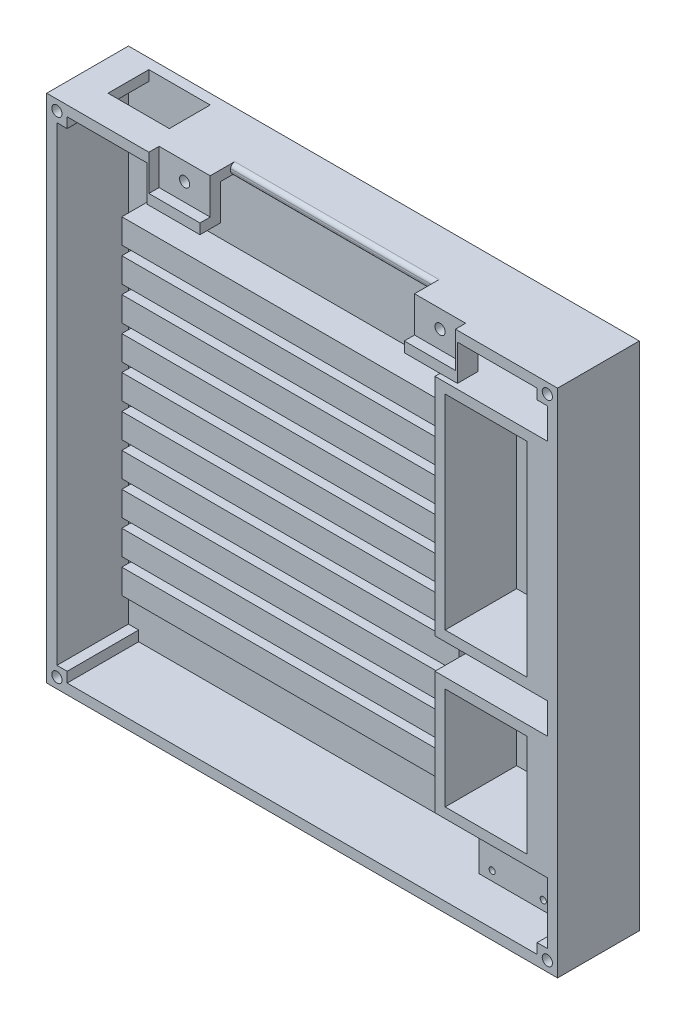
SolidWorks part; units mm, degrees
ref_plane "Ebene vorne" through (0, 0, 0) normal (0, 0, 1) x (1, 0, 0)
ref_plane "Ebene oben" through (0, 0, 0) normal (0, 1, 0) x (1, 0, 0)
ref_plane "Ebene rechts" through (0, 0, 0) normal (1, 0, 0) x (0, 0, -1)
sketch "Sketch1" plane through (0, 0, 0) normal (0, 0, 1) x (1, 0, 0)
  line L1 (0, 0) -> (-250, 0)
  line L2 (0, 0) -> (0, 250)
  line L3 (0, 250) -> (-250, 250)
  line L4 (-250, 0) -> (-250, 250)
  dimension "D1" = 250
  dimension "D2" = 250
extrude "Boss-Extrude1" add sketch "Sketch1" along normal blind 50
sketch "Sketch2" plane through (0, 0, 50) normal (0, 0, 1) x (1, 0, 0)
  line L0 (-125, 250) -> (-125, 0) construction
  line L1 (0, 250) -> (-250, 250) construction
  line L2 (-250, 0) -> (0, 0) construction
  line L5 (0, 0) -> (0, 250) construction
  line L7 (-55, 220) -> (-15, 220)
  line L8 (-55, 220) -> (-55, 120)
  line L9 (-55, 120) -> (-15, 120)
  line L10 (-15, 220) -> (-15, 120)
  line L14 (-55, 95) -> (-15, 95)
  line L15 (-55, 95) -> (-55, 45)
  line L16 (-55, 45) -> (-15, 45)
  line L17 (-15, 95) -> (-15, 45)
  dimension "D1" = 100
  dimension "D2" = 40
  dimension "D3" = 30
  dimension "D4" = 15
  dimension "D5" = 50
  dimension "D6" = 25
extrude "Cut-Extrude1" cut sketch "Sketch2" against normal blind 45
fillet "Fillet1" radius 5 4 edges at (-35, 120, 50) (-15, 170, 50) (-55, 170, 50) (-35, 220, 50)
fillet "Fillet2" radius 5 4 edges at (-35, 45, 50) (-15, 70, 50) (-35, 95, 50) (-55, 70, 50)
sketch "Sketch4" plane through (0, 0, 50) normal (0, 0, 1) x (1, 0, 0)
  line L0 (0, 250) -> (-250, 250) construction
  line L1 (-200, 250) -> (-175, 250)
  line L2 (-200, 250) -> (-200, 232.5)
  line L3 (-200, 232.5) -> (-175, 232.5)
  line L4 (-175, 250) -> (-175, 232.5)
  line L5 (-125, 250) -> (-125, 0) construction
  line L10 (-250, 0) -> (0, 0) construction
  line L11 (-50, 232.5) -> (-75, 232.5)
  line L12 (-75, 250) -> (-75, 232.5)
  line L13 (-50, 250) -> (-75, 250)
  line L14 (-50, 250) -> (-50, 232.5)
  dimension "D1" = 50
  dimension "D2" = 25
  dimension "D3" = 17.5
sketch "Sketch5" plane through (0, 0, 50) normal (0, 0, 1) x (1, 0, 0)
  line L0 (-233.25, 198.25) -> (-68.25, 198.25) construction
  line L2 (-68.25, 198.25) -> (-68.25, 33.25) construction
  line L3 (-68.25, 33.25) -> (-233.25, 33.25) construction
  line L4 (-233.25, 33.25) -> (-233.25, 198.25) construction
  line L5 (-250, 250) -> (-250, 0) construction
  line L9 (-233.25, 198.25) -> (-216.75, 198.25) construction
  line L10 (-233.25, 198.25) -> (-233.25, 181.75) construction
  line L11 (-233.25, 181.75) -> (-216.75, 181.75) construction
  line L12 (-216.75, 198.25) -> (-216.75, 181.75) construction
  line L13 (-233.25, 198.25) -> (-216.75, 181.75) construction
  line L14 (-233.25, 181.75) -> (-216.75, 198.25) construction
  line L16 (0, 250) -> (-250, 250) construction
  circle A0 centre (-225, 190) radius 6.25
  dimension "D5" = 12.5
  dimension "D1" = 165
  dimension "D2" = 51.75
  dimension "D3" = 16.75
  dimension "D4" = 165
  dimension "D6" = 16.5
  dimension "D7" = 16.5
extrude "Cut-Extrude2" cut sketch "Sketch5" against normal blind 22
fillet "Fillet5" radius 1.5 1 edges at (-218.75, 190, 50)
pattern_linear "LPattern4" count 10 spacing 16.5 along (1, 0, 0) count 10 spacing 16.5 along (0, -1, 0) of "Cut-Extrude2", "Fillet5"
sketch "Sketch7" plane through (0, 0, 0) normal (0, 0, -1) x (-1, 0, 0)
  line L0 (250, 250) -> (250, 0) construction
  line L1 (5, 245) -> (245, 245)
  line L2 (5, 245) -> (5, 225)
  line L3 (5, 5) -> (245, 5)
  line L4 (245, 245) -> (245, 5)
  line L5 (0, 250) -> (250, 250) construction
  line L6 (0, 0) -> (0, 250) construction
  line L7 (250, 0) -> (0, 0) construction
  line L8 (5, 115) -> (5, 100)
  line L9 (5, 225) -> (60, 225)
  line L11 (5, 115) -> (60, 115)
  line L12 (60, 225) -> (60, 115)
  line L13 (5, 40) -> (60, 40)
  line L15 (5, 100) -> (60, 100)
  line L16 (60, 40) -> (60, 100)
  line L17 (5, 40) -> (5, 5)
  line L18 (60, 225) -> (10, 225) construction
  dimension "D1" = 5
  dimension "D2" = 5
  dimension "D3" = 5
  dimension "D4" = 5
extrude "Cut-Extrude4" cut sketch "Sketch7" against normal blind 45
sketch "Sketch8" plane through (0, 0, 50) normal (0, 0, 1) x (1, 0, 0)
  line L0 (0, 250) -> (-250, 250) construction
  line L1 (-175, 250) -> (-75, 250)
  line L2 (-175, 250) -> (-175, 230)
  line L3 (-175, 230) -> (-75, 230)
  line L4 (-75, 250) -> (-75, 230)
  point P6 (-125, 250)
  point P7 (-125, 250)
  dimension "D1" = 100
  dimension "D2" = 20
extrude "Cut-Extrude5" cut sketch "Sketch8" against normal blind 20
fillet "Fillet6" radius 2.5 2 edges at (-125, 230, 45) (-125, 230, 50)
fillet "Fillet7" radius 2 2 edges at (-125, 250, 30) (-125, 245, 30)
sketch "Sketch10" plane through (0, 0, 50) normal (0, 0, 1) x (1, 0, 0)
  line L2 (-35, 40) -> (-35, 0) construction
  line L3 (-10, 40) -> (-60, 40) construction
  line L4 (-250, 0) -> (0, 0) construction
  circle A0 centre (-35, 20) radius 13.5
  dimension "D1" = 27
extrude "Cut-Extrude6" cut sketch "Sketch10" against normal through all
extrude "Cut-Extrude7" cut sketch "Sketch4" against normal blind 10
sketch "Sketch12" plane through (0, 0, 45) normal (0, 0, -1) x (-1, 0, 0)
  line L0 (17.3, 19.25) -> (51.5, 19.25) construction
  line L1 (17.3, 32.5) -> (51.5, 32.5) construction
  line L2 (17.3, 32.5) -> (17.3, 6) construction
  line L3 (17.3, 6) -> (51.5, 6) construction
  line L4 (51.5, 32.5) -> (51.5, 6) construction
  line L5 (35, 40) -> (35, 0) construction
  line L6 (17.3, 20) -> (51.5, 20) construction
  circle A0 centre (46.4, 29.3) radius 2.5
  circle A2 centre (20.1, 29.3) radius 2.5
  circle A3 centre (20.1, 29.3) radius 1.5
  circle A4 centre (46.4, 29.3) radius 1.5
  circle A5 centre (20.1, 9.2) radius 1.5
  circle A6 centre (20.1, 9.2) radius 2.5
  circle A7 centre (46.4, 9.2) radius 1.5
  circle A8 centre (46.4, 9.2) radius 2.5
  dimension "D3" = 5
  dimension "D4" = 2.8
  dimension "D5" = 3.2
  dimension "D6" = 5
  dimension "D7" = 5.1
  dimension "D9" = 3
  dimension "D10" = 3
  dimension "D1" = 34.2
  dimension "D2" = 26.5
  dimension "D8" = 3.2
  dimension "D11" = 16.5
  dimension "D12" = 13.25
  dimension "D13" = 14
fillet "Verrundung1" radius 2.5 2 edges at (-48.5, 20, 45) (-21.5, 20, 50)
sketch "Skizze2" plane through (0, 245, 0) normal (0, -1, 0) x (1, 0, 0)
  line L0 (-175, 28) -> (-175, 40) construction
  line L1 (-175, 40) -> (-200, 40)
  line L2 (-175, 40) -> (-175, 35)
  line L3 (-175, 35) -> (-200, 35)
  line L4 (-200, 40) -> (-200, 35)
  line L5 (-200, 40) -> (-175, 40) construction
  line L6 (-125, 50) -> (-125, 0) construction
  line L7 (-250, 50) -> (0, 50) construction
  line L8 (-250, 0) -> (0, 0) construction
  line L9 (-50, 40) -> (-50, 35)
  line L10 (-75, 35) -> (-50, 35)
  line L11 (-75, 40) -> (-75, 35)
  line L12 (-75, 40) -> (-50, 40)
  dimension "D1" = 25
  dimension "D2" = 5
extrude "Aufsatz-Linear austragen1" add sketch "Skizze2" along normal blind 12.5
sketch "Skizze4" plane through (0, 0, 45) normal (0, 0, -1) x (-1, 0, 0)
  line L0 (75, 232.5) -> (75, 227.5) construction
  line L1 (50, 232.5) -> (75, 232.5)
  line L3 (49, 227.5) -> (75, 227.5)
  line L4 (75, 232.5) -> (75, 227.5)
  line L5 (175, 227.5) -> (175, 232.5) construction
  line L6 (200, 232.5) -> (175, 232.5)
  line L8 (201, 227.5) -> (175, 227.5)
  line L9 (175, 232.5) -> (175, 227.5)
  line L10 (50, 245) -> (5, 245) construction
  line L12 (50, 232.5) -> (50, 245)
  line L13 (50, 245) -> (49, 245)
  line L14 (49, 227.5) -> (49, 245)
  line L15 (245, 245) -> (200, 245) construction
  line L17 (200, 232.5) -> (200, 245)
  line L18 (200, 245) -> (201, 245)
  line L19 (201, 227.5) -> (201, 245)
  dimension "D1" = 5
  dimension "D2" = 5
  dimension "D3" = 1
  dimension "D4" = 1
extrude "Aufsatz-Linear austragen2" add sketch "Skizze4" along normal blind 10
sketch "Skizze11" plane through (0, 0, 50) normal (0, 0, 1) x (1, 0, 0)
  line L1 (-232.75, 197.75) -> (-68.75, 197.75)
  line L2 (-232.75, 197.75) -> (-232.75, 33.75)
  line L3 (-232.75, 33.75) -> (-68.75, 33.75)
  line L4 (-68.75, 197.75) -> (-68.75, 33.75)
  circle A0 centre (-175.5, 190) radius 7.75 construction
  circle A1 centre (-225, 173.5) radius 7.75 construction
  circle A2 centre (-76.5, 157) radius 7.75 construction
  circle A3 centre (-159, 41.5) radius 7.75 construction
extrude "Schnitt-Linear austragen6" cut sketch "Skizze11" against normal blind 10
sketch "Skizze12" plane through (0, 0, 50) normal (0, 0, 1) x (1, 0, 0)
  line L18 (-237.75, 28.75) -> (-63.75, 28.75)
  line L19 (-63.75, 28.75) -> (-63.75, 202.75)
  line L20 (-237.75, 202.75) -> (-237.75, 28.75)
  line L21 (-63.75, 202.75) -> (-237.75, 202.75)
  line L22 (-237.75, 28.75) -> (-63.75, 28.75)
  line L23 (-63.75, 28.75) -> (-63.75, 202.75)
  line L24 (-237.75, 202.75) -> (-237.75, 28.75)
  line L25 (-63.75, 202.75) -> (-237.75, 202.75)
  dimension "D1" = 5
extrude "Schnitt-Linear austragen7" cut sketch "Skizze12" against normal blind 2.5
sketch "Skizze13" plane through (0, 0, 47.5) normal (0, 0, 1) x (1, 0, 0)
  line L0 (-232.75, 115.75) -> (-237.75, 115.75) construction
  line L1 (-232.75, 33.75) -> (-232.75, 197.75) construction
  line L2 (-237.75, 202.75) -> (-237.75, 28.75) construction
  line L3 (-150.75, 202.75) -> (-150.75, 197.75) construction
  line L4 (-63.75, 202.75) -> (-237.75, 202.75) construction
  line L5 (-232.75, 197.75) -> (-68.75, 197.75) construction
  line L6 (-68.75, 115.75) -> (-63.75, 115.75) construction
  line L7 (-68.75, 197.75) -> (-68.75, 33.75) construction
  line L8 (-63.75, 28.75) -> (-63.75, 202.75) construction
  line L9 (-150.75, 33.75) -> (-150.75, 28.75) construction
  line L10 (-68.75, 33.75) -> (-232.75, 33.75) construction
  line L11 (-237.75, 28.75) -> (-63.75, 28.75) construction
  circle A0 centre (-235.25, 200.25) radius 1.5
  circle A1 centre (-150.75, 200.25) radius 1.5
  circle A2 centre (-66.25, 200.25) radius 1.5
  circle A3 centre (-235.25, 115.75) radius 1.5
  circle A4 centre (-66.25, 115.75) radius 1.5
  circle A5 centre (-66.25, 31.25) radius 1.5
  circle A6 centre (-150.75, 31.25) radius 1.5
  circle A7 centre (-235.25, 31.25) radius 1.5
  point P27 (-235.25, 115.75)
  point P28 (-150.75, 200.25)
  point P33 (-66.25, 115.75)
  dimension "D1" = 3
  dimension "D2" = 3
  dimension "D3" = 3
  dimension "D4" = 3
  dimension "D5" = 3
extrude "Schnitt-Linear austragen8" cut sketch "Skizze13" against normal blind 2.5
sketch "Skizze14" plane through (0, 0, 45) normal (0, 0, -1) x (-1, 0, 0)
  line L1 (0, 250) -> (10, 250)
  line L2 (0, 250) -> (0, 240)
  line L3 (0, 240) -> (10, 240)
  line L4 (10, 250) -> (10, 240)
  line L5 (240, 240) -> (250, 240)
  line L6 (250, 250) -> (250, 240)
  line L7 (240, 250) -> (250, 250)
  line L8 (240, 250) -> (240, 240)
  line L9 (240, 0) -> (250, 0)
  line L10 (250, 10) -> (250, 0)
  line L11 (240, 10) -> (250, 10)
  line L12 (240, 10) -> (240, 0)
  line L13 (0, 0) -> (10, 0)
  line L14 (10, 10) -> (10, 0)
  line L15 (0, 10) -> (10, 10)
  line L16 (0, 10) -> (0, 0)
  line L17 (250, 250) -> (250, 0) construction
  line L18 (250, 0) -> (0, 0) construction
  dimension "D1" = 10
  dimension "D2" = 10
  dimension "D3" = 2
  dimension "D4" = 2
extrude "Aufsatz-Linear austragen3" add sketch "Skizze14" along direction (0, 0, 1) on the side of the normal up to surface (45 mm away) up to face at (-63.3333, 121.6667, 0)
sketch "Skizze16" plane through (-250, 0, 0) normal (-1, 0, 0) x (0, 0, 1)
  line L0 (50, 0) -> (0, 0) construction
  line L1 (50, 250) -> (45, 250)
  line L2 (50, 250) -> (50, 0)
  line L3 (50, 0) -> (45, 0)
  line L4 (45, 250) -> (45, 0)
  line L5 (50, 250) -> (50, 0) construction
  dimension "D1" = 5
extrude "Schnitt-Linear austragen9" cut sketch "Skizze16" against normal through all
ref_plane "Ebene1" through (0, 0, 10) normal (0, 0, 1) x (1, 0, 0)
sketch "Skizze18" plane through (0, 0, 45) normal (0, 0, 1) x (1, 0, 0)
  line L0 (-5, 40) -> (-5, 10) construction
  line L4 (-245, 10) -> (-245, 240) construction
  line L6 (-240, 245) -> (-201, 245) construction
  line L10 (-49, 245) -> (-10, 245) construction
  line L16 (-10, 5) -> (-240, 5) construction
  line L17 (-5, 240) -> (-5, 225) construction
  circle A0 centre (-245, 245) radius 2.5
  circle A1 centre (-5, 245) radius 2.5
  circle A2 centre (-5, 5) radius 2.5
  circle A3 centre (-245, 5) radius 2.5
  dimension "D1" = 5
  dimension "D2" = 5
  dimension "D3" = 5
  dimension "D4" = 5
extrude "Schnitt-Linear austragen10" cut sketch "Skizze18" against normal blind 10
sketch "Skizze21" plane through (0, 0, 0) normal (0, 0, -1) x (-1, 0, 0)
  line L1 (0, 250) -> (250, 250)
  line L2 (0, 250) -> (0, 0)
  line L3 (0, 0) -> (250, 0)
  line L4 (250, 250) -> (250, 0)
extrude "Schnitt-Linear austragen13" cut sketch "Skizze21" against normal blind 10
sketch "Skizze25" plane through (0, 0, 10) normal (0, 0, -1) x (-1, 0, 0)
  line L1 (0, 250) -> (250, 250)
  line L2 (0, 250) -> (0, 0)
  line L3 (0, 0) -> (250, 0)
  line L4 (250, 250) -> (250, 0)
extrude "Aufsatz-Linear austragen7" add sketch "Skizze25" along normal blind 5
sketch "Skizze26" plane through (0, 0, 10) normal (0, 0, 1) x (1, 0, 0)
  line L0 (-35, 45) -> (-35, 5) construction
  line L1 (-55, 45) -> (-15, 45) construction
  line L2 (-240, 5) -> (-10, 5) construction
  line L3 (-23.5, 13) -> (-20.5, 13) construction
  line L4 (-52.5, 37) -> (-18.5, 37) construction
  line L5 (-52.5, 37) -> (-52.5, 11) construction
  line L6 (-52.5, 11) -> (-18.5, 11) construction
  line L7 (-18.5, 37) -> (-18.5, 11) construction
  line L8 (-43, 33) -> (-27, 33) construction
  line L9 (-43, 33) -> (-43, 17) construction
  line L10 (-43, 17) -> (-27, 17) construction
  line L11 (-27, 33) -> (-27, 17) construction
  line L12 (-48.5, 32) -> (-45.5, 32) construction
  line L13 (-48.5, 32) -> (-48.5, 35) construction
  line L14 (-48.5, 35) -> (-45.5, 35) construction
  line L15 (-45.5, 32) -> (-45.5, 35) construction
  line L16 (-48.5, 32) -> (-45.5, 35) construction
  line L17 (-48.5, 35) -> (-45.5, 32) construction
  line L18 (-23.5, 13) -> (-23.5, 16) construction
  line L19 (-23.5, 16) -> (-20.5, 16) construction
  line L20 (-20.5, 13) -> (-20.5, 16) construction
  line L21 (-23.5, 13) -> (-20.5, 16) construction
  line L22 (-23.5, 16) -> (-20.5, 13) construction
  line L23 (-48.5, 13) -> (-45.5, 13) construction
  line L24 (-48.5, 13) -> (-48.5, 16) construction
  line L25 (-48.5, 16) -> (-45.5, 16) construction
  line L26 (-45.5, 13) -> (-45.5, 16) construction
  line L27 (-48.5, 13) -> (-45.5, 16) construction
  line L28 (-48.5, 16) -> (-45.5, 13) construction
  line L29 (-23.5, 32) -> (-20.5, 32) construction
  line L30 (-23.5, 32) -> (-23.5, 35) construction
  line L31 (-23.5, 35) -> (-20.5, 35) construction
  line L32 (-20.5, 32) -> (-20.5, 35) construction
  line L33 (-23.5, 32) -> (-20.5, 35) construction
  line L34 (-23.5, 35) -> (-20.5, 32) construction
  line L35 (-53.5, 38) -> (-17.5, 38)
  line L36 (-17.5, 38) -> (-17.5, 10)
  line L37 (-53.5, 10) -> (-17.5, 10)
  line L38 (-53.5, 38) -> (-53.5, 10)
  circle A0 centre (-47, 33.5) radius 1.5
  circle A1 centre (-22, 14.5) radius 1.5
  circle A2 centre (-47, 14.5) radius 1.5
  circle A3 centre (-22, 33.5) radius 1.5
  point P14 (-35, 33)
  point P15 (-35, 25)
  point P16 (-43, 25)
  dimension "D6" = 3
  dimension "D9" = 3
  dimension "D10" = 3
  dimension "D11" = 3
  dimension "D1" = 34
  dimension "D2" = 26
  dimension "D3" = 16
  dimension "D4" = 4
  dimension "D5" = 9.5
  dimension "D7" = 4
  dimension "D8" = 2
  dimension "D12" = 2
  dimension "D13" = 2
  dimension "D14" = 2
  dimension "D15" = 2
  dimension "D16" = 4
  dimension "D17" = 2
  dimension "D18" = 1
extrude "Aufsatz-Linear austragen8" add sketch "Skizze26" along normal blind 20
sketch "Skizze27" plane through (0, 0, 10) normal (0, 0, 1) x (1, 0, 0)
  line L0 (-233.25, 179.5) -> (-233.25, 167.5)
  line L1 (-233.25, 198.25) -> (-68.25, 198.25) construction
  line L2 (-233.25, 198.25) -> (-233.25, 33.25) construction
  line L3 (-233.25, 33.25) -> (-68.25, 33.25) construction
  line L4 (-68.25, 198.25) -> (-68.25, 33.25) construction
  line L5 (-233.25, 196) -> (-68.25, 196)
  line L6 (-233.25, 196) -> (-233.25, 184)
  line L7 (-233.25, 184) -> (-68.25, 184)
  line L8 (-68.25, 196) -> (-68.25, 184)
  line L9 (-233.25, 179.5) -> (-68.25, 179.5)
  line L10 (-68.25, 179.5) -> (-68.25, 167.5)
  line L11 (-233.25, 167.5) -> (-68.25, 167.5)
  line L12 (-233.25, 163) -> (-233.25, 151)
  line L13 (-233.25, 163) -> (-68.25, 163)
  line L14 (-68.25, 163) -> (-68.25, 151)
  line L15 (-233.25, 151) -> (-68.25, 151)
  line L16 (-233.25, 146.5) -> (-233.25, 134.5)
  line L17 (-233.25, 146.5) -> (-68.25, 146.5)
  line L18 (-68.25, 146.5) -> (-68.25, 134.5)
  line L19 (-233.25, 134.5) -> (-68.25, 134.5)
  line L20 (-233.25, 130) -> (-233.25, 118)
  line L21 (-233.25, 130) -> (-68.25, 130)
  line L22 (-68.25, 130) -> (-68.25, 118)
  line L23 (-233.25, 118) -> (-68.25, 118)
  line L24 (-233.25, 113.5) -> (-233.25, 101.5)
  line L25 (-233.25, 113.5) -> (-68.25, 113.5)
  line L26 (-68.25, 113.5) -> (-68.25, 101.5)
  line L27 (-233.25, 101.5) -> (-68.25, 101.5)
  line L28 (-233.25, 97) -> (-233.25, 85)
  line L29 (-233.25, 97) -> (-68.25, 97)
  line L30 (-68.25, 97) -> (-68.25, 85)
  line L31 (-233.25, 85) -> (-68.25, 85)
  line L32 (-233.25, 80.5) -> (-233.25, 68.5)
  line L33 (-233.25, 80.5) -> (-68.25, 80.5)
  line L34 (-68.25, 80.5) -> (-68.25, 68.5)
  line L35 (-233.25, 68.5) -> (-68.25, 68.5)
  line L36 (-233.25, 64) -> (-233.25, 52)
  line L37 (-233.25, 64) -> (-68.25, 64)
  line L38 (-68.25, 64) -> (-68.25, 52)
  line L39 (-233.25, 52) -> (-68.25, 52)
  line L40 (-233.25, 47.5) -> (-233.25, 35.5)
  line L41 (-233.25, 47.5) -> (-68.25, 47.5)
  line L42 (-68.25, 47.5) -> (-68.25, 35.5)
  line L43 (-233.25, 35.5) -> (-68.25, 35.5)
  point P10 (-233.25, 190)
  dimension "D1" = 12
  dimension "D3" = 4.5
  dimension "D2" = 10
extrude "Aufsatz-Linear austragen9" add sketch "Skizze27" along normal blind 15
sketch "Skizze28" plane through (0, 250, 0) normal (0, 1, 0) x (1, 0, 0)
  line L0 (-250, -45) -> (-250, -5) construction
  line L1 (-205, -30) -> (-235, -30)
  line L2 (-205, -30) -> (-205, -10)
  line L3 (-205, -10) -> (-235, -10)
  line L4 (-235, -30) -> (-235, -10)
  line L5 (-250, -5) -> (0, -5) construction
  dimension "D1" = 15
  dimension "D2" = 5
  dimension "D3" = 30
  dimension "D4" = 20
extrude "Schnitt-Linear austragen14" cut sketch "Skizze28" against normal blind 15
sketch "Skizze29" plane through (0, 0, 40) normal (0, 0, 1) x (1, 0, 0)
  line L0 (-187.5, 250) -> (-187.5, 232.5) construction
  line L1 (-175, 250) -> (-200, 250) construction
  line L2 (-200, 232.5) -> (-175, 232.5) construction
  line L3 (-200, 241.25) -> (-175, 241.25) construction
  line L4 (-200, 250) -> (-200, 232.5) construction
  line L5 (-175, 232.5) -> (-175, 250) construction
  line L6 (-62.5, 250) -> (-62.5, 232.5) construction
  line L7 (-50, 250) -> (-75, 250) construction
  line L8 (-75, 232.5) -> (-50, 232.5) construction
  line L9 (-75, 241.25) -> (-50, 241.25) construction
  line L10 (-75, 250) -> (-75, 232.5) construction
  line L11 (-50, 232.5) -> (-50, 250) construction
  circle A0 centre (-187.5, 241.25) radius 2.5
  circle A2 centre (-62.5, 241.25) radius 2.5
  dimension "D1" = 5
  dimension "D2" = 5
extrude "Schnitt-Linear austragen15" cut sketch "Skizze29" against normal blind 15
